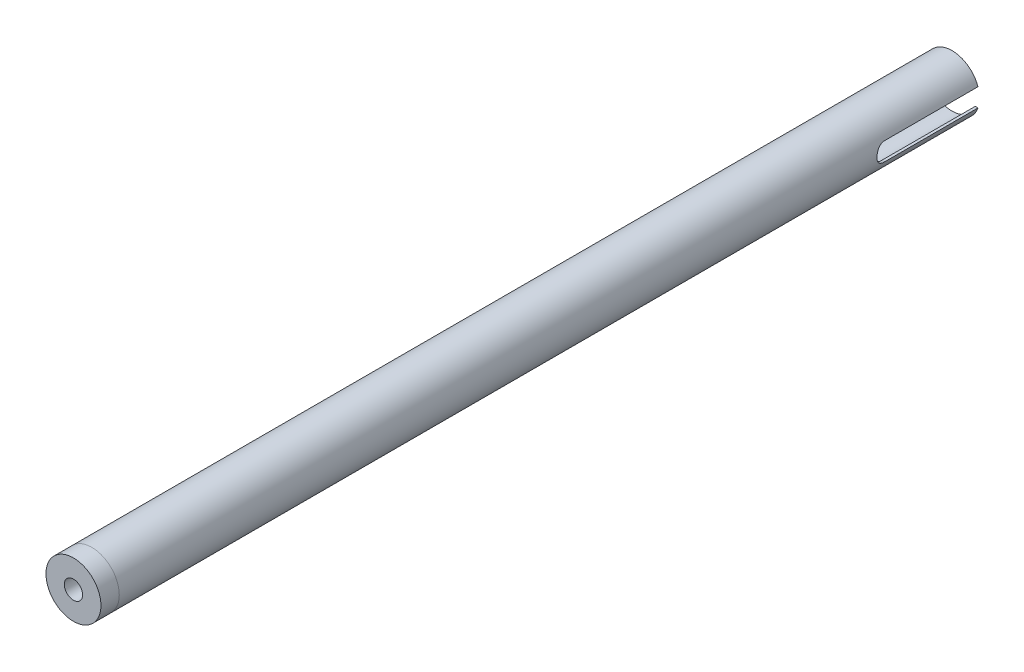
SolidWorks part; units mm, degrees
material "AISI 4130 Steel, normalized at 870C"
ref_plane "Front Plane" through (0, 0, 0) normal (0, 0, 1) x (1, 0, 0)
ref_plane "Top Plane" through (0, 0, 0) normal (0, 1, 0) x (1, 0, 0)
ref_plane "Right Plane" through (0, 0, 0) normal (1, 0, 0) x (0, 0, -1)
sketch "Axis" plane through (0, 0, 0) normal (0, 1, 0) x (1, 0, 0)
  line L0 (0, 0) -> (0, 304.3801) construction
  line L1 (0, 0) -> (0, -21.9075) construction
  line L2 (0, 304.3801) -> (-9.525, 304.3801) construction
  line L4 (0, 332.3201) -> (-22.1542, 267.3343) construction
  dimension "D1" = 21.9075
  dimension "D2" = 9.525
sketch "Sketch1" plane through (0, 0, 0) normal (0, 0, 1) x (1, 0, 0)
  line L0 (-9.525, 0) -> (9.525, 0) construction
  line L1 (-8.9803, 3.175) -> (8.9803, 3.175)
  line L2 (-8.9803, -3.175) -> (8.9803, -3.175)
  circle A0 centre (0, 0) radius 9.525
  circle A1 centre (0, 0) radius 8.636
  circle A2 centre (0, 0) radius 3.175
  dimension "D1" = 19.05
  dimension "D3" = 6.35
  dimension "D2" = 0.889
  dimension "D4" = 6.35
extrude "Threaded insert 1-1" add sketch "Sketch1" against normal blind 6.35 contours A2 L1 A1 | A1 L1 A0 | A2 L0 A1 L1 | A1 L0 A0 L1 | L0 A1 L2 A0 | L0 A2 L2 A1 | A2 L2 A1 | A1 L2 A0 | L0 A1 L2 A2 | L0 A0 L2 A1 | A0 L0 A1 L1 | A1 L0 A2 L1 region at (5.4259, 1.6615, 0) region at (5.4259, -1.6615, 0) region at (8.8881, 1.6046, 0) region at (8.8881, -1.6046, 0) region at (-5.4259, -1.6615, 0) region at (-5.4259, 1.6615, 0) region at (0, 5.4321, 0) region at (0, -5.4321, 0) region at (0, 8.8265, 0) region at (8.5057, -3.3655, 0) region at (-8.8881, -1.6046, 0) region at (-8.8881, 1.6046, 0)
extrude "Threaded insert 1-2" add sketch "Sketch1<3>" against normal blind 6.35 from surface contours A2 L1 A1 | A2 L0 A1 L1 | L0 A2 L2 A1 | A2 L2 A1 | L0 A1 L2 A2 | A1 L0 A2 L1 region at (5.4259, 1.6615, 0) region at (5.4259, -1.6615, 0) region at (-5.4259, -1.6615, 0) region at (-5.4259, 1.6615, 0) region at (0, 5.4321, 0) region at (0, -5.4321, 0) starting at face at (9.525, 0, -6.35)
sketch "Sketch1<3>" plane through (0, 0, 0) normal (0, 0, 1) x (1, 0, 0) same geometry as "Sketch1"
extrude "A-arm tube" add sketch "Sketch1<4>" against normal up to vertex (304.3801 mm away) from surface separate body contours A1 L1 A0 | A1 L0 A0 L1 | L0 A1 L2 A0 | A1 L2 A0 | L0 A0 L2 A1 | A0 L0 A1 L1 region at (8.8881, 1.6046, 0) region at (8.8881, -1.6046, 0) region at (0, 8.8265, 0) region at (8.5057, -3.3655, 0) region at (-8.8881, -1.6046, 0) region at (-8.8881, 1.6046, 0) up to point (0, 0, -304.3801) starting at face at (8.636, 0, -6.35)
sketch "Sketch1<4>" plane through (0, 0, 0) normal (0, 0, 1) x (1, 0, 0) same geometry as "Sketch1"
extrude "Apex slot" cut sketch "Sketch1<5>" along normal blind 35.56 from surface contours A0 L0 A1 L1 | L0 A0 L2 A1 | A1 L0 A0 L1 | L0 A1 L2 A0 region at (8.8881, 1.6046, 0) region at (8.8881, -1.6046, 0) region at (-8.8881, -1.6046, 0) region at (-8.8881, 1.6046, 0) starting at face at (8.636, 0, -304.3801)
sketch "Sketch1<5>" plane through (0, 0, 0) normal (0, 0, 1) x (1, 0, 0) same geometry as "Sketch1"
fillet "Fillet1" radius 3.175 4 edges at (-8.5057, 3.175, -268.8201) (-8.5057, -3.175, -268.8201) (8.5057, -3.175, -268.8201) (8.5057, 3.175, -268.8201)
equation "\"tube diameter\"= 3 / 4"
equation "\"tube thickness\"= .035"
equation "\"apex thickness\"= .25"
equation "\"tube slot\"= 1.4"
equation "\"D1@Sketch1\"=\"tube diameter\""
equation "\"D2@Sketch1\"=\"tube thickness\""
equation "\"threaded insert hole\"= 1 / 4"
equation "\"D3@Sketch1\"=\"threaded insert hole\""
equation "\"D4@Sketch1\"=\"apex thickness\""
equation "\"D1@Apex slot\" = \"tube slot\""
equation "\"D1@Fillet1\"=\"apex thickness\"/2"
equation "\"D2@Axis\"=\"tube diameter\"/2"
